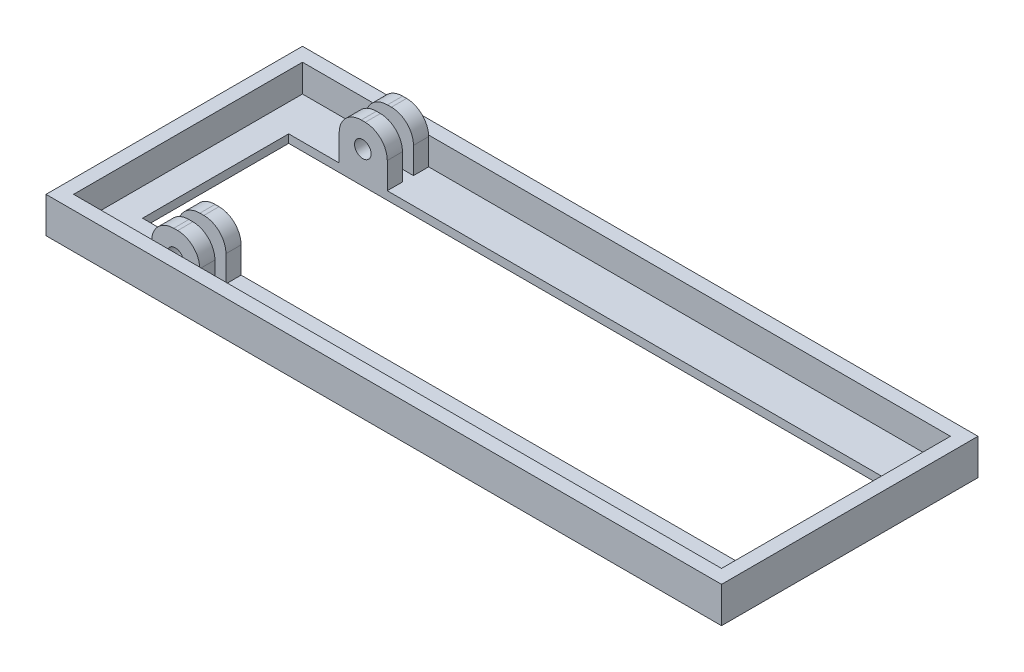
SolidWorks part; units mm, degrees
ref_plane "Front Plane" through (0, 0, 0) normal (0, 0, 1) x (1, 0, 0)
ref_plane "Top Plane" through (0, 0, 0) normal (0, 1, 0) x (1, 0, 0)
ref_plane "Right Plane" through (0, 0, 0) normal (1, 0, 0) x (0, 0, -1)
sketch "Sketch1" plane through (0, 0, 0) normal (0, 1, 0) x (1, 0, 0)
  line L0 (1125.8144, 1330.2208) -> (1275.8144, 1330.2208) construction
  line L1 (1275.8144, 1330.2208) -> (1275.8144, 1130.2208) construction
  line L2 (3575.3144, 400.2208) -> (3575.3144, 600.2208) construction
  line L3 (3575.3144, 600.2208) -> (3425.3144, 600.2208) construction
  line L5 (1275.8144, 1130.2208) -> (3425.3144, 1130.2208)
  line L6 (1275.8144, 1130.2208) -> (1275.8144, 600.2208)
  line L7 (1275.8144, 600.2208) -> (3425.3144, 600.2208)
  line L8 (3425.3144, 1130.2208) -> (3425.3144, 600.2208)
  line L13 (1125.8144, 1330.2208) -> (3575.3144, 1330.2208)
  line L14 (1125.8144, 1330.2208) -> (1125.8144, 400.2208)
  line L15 (1125.8144, 400.2208) -> (3575.3144, 400.2208)
  line L16 (3575.3144, 1330.2208) -> (3575.3144, 400.2208)
sketch "Sketch4" plane through (0, 0, 0) normal (0, 1, 0) x (1, 0, 0)
  line L0 (1125.8144, 1330.2208) -> (1275.8144, 1330.2208) construction
  line L1 (1275.8144, 1330.2208) -> (1275.8144, 1130.2208) construction
  line L2 (3575.3144, 400.2208) -> (3575.3144, 600.2208) construction
  line L3 (3575.3144, 600.2208) -> (3425.3144, 600.2208) construction
  line L4 (1275.8144, 1130.2208) -> (3425.3144, 1130.2208)
  line L5 (1275.8144, 1130.2208) -> (1275.8144, 600.2208)
  line L6 (1275.8144, 600.2208) -> (3425.3144, 600.2208)
  line L7 (3425.3144, 1130.2208) -> (3425.3144, 600.2208)
  line L8 (1125.8144, 1330.2208) -> (3575.3144, 1330.2208)
  line L9 (1125.8144, 1330.2208) -> (1125.8144, 400.2208)
  line L10 (1125.8144, 400.2208) -> (3575.3144, 400.2208)
  line L11 (3575.3144, 1330.2208) -> (3575.3144, 400.2208)
extrude "Boss-Extrude2" add sketch "Sketch4" along normal blind 30
sketch "Sketch5" plane through (0, 30, 0) normal (0, 1, 0) x (1, 0, 0)
  line L0 (1175.8144, 1280.2208) -> (1175.8144, 450.2208)
  line L1 (2350.5644, 1330.2208) -> (2350.5644, 400.2208) construction
  line L2 (3575.3144, 1330.2208) -> (1125.8144, 1330.2208) construction
  line L3 (1125.8144, 1330.2208) -> (1125.8144, 400.2208)
  line L4 (1125.8144, 400.2208) -> (3575.3144, 400.2208)
  line L5 (3575.3144, 1330.2208) -> (3575.3144, 400.2208)
  line L6 (3525.3144, 1280.2208) -> (3525.3144, 450.2208)
  line L9 (1125.8144, 400.2208) -> (3575.3144, 400.2208) construction
  line L10 (1175.8144, 1280.2208) -> (3525.3144, 1280.2208)
  line L11 (1175.8144, 450.2208) -> (3525.3144, 450.2208)
  line L12 (3575.3144, 1330.2208) -> (1125.8144, 1330.2208)
  point P7 (2350.5644, 450.2208)
  point P17 (2350.5644, 1280.2208)
sketch "Sketch6" plane through (0, 30, 0) normal (0, 1, 0) x (1, 0, 0)
  line L0 (1175.8144, 1280.2208) -> (1175.8144, 450.2208)
  line L1 (2350.5644, 1330.2208) -> (2350.5644, 400.2208) construction
  line L2 (1125.8144, 1330.2208) -> (1125.8144, 400.2208)
  line L3 (1125.8144, 400.2208) -> (3575.3144, 400.2208)
  line L4 (3575.3144, 1330.2208) -> (3575.3144, 400.2208)
  line L5 (3525.3144, 1280.2208) -> (3525.3144, 450.2208)
  line L6 (1175.8144, 1280.2208) -> (3525.3144, 1280.2208)
  line L7 (1175.8144, 450.2208) -> (3525.3144, 450.2208)
  line L8 (3575.3144, 1330.2208) -> (1125.8144, 1330.2208)
  point P6 (2350.5644, 450.2208)
  point P10 (2350.5644, 1280.2208)
extrude "Boss-Extrude3" add sketch "Sketch6" along normal blind 100
sketch "Sketch7" plane through (0, 30, 0) normal (0, 1, 0) x (1, 0, 0)
  line L0 (1275.8144, 1130.2208) -> (1546.0948, 1130.2208) construction
  line L1 (3425.3144, 1130.2208) -> (1275.8144, 1130.2208) construction
  line L2 (3525.3144, 1280.2208) -> (1175.8144, 1280.2208) construction
  line L3 (1275.8144, 865.2208) -> (3425.3144, 865.2208) construction
  line L4 (1458.8863, 1130.2208) -> (1458.8863, 1280.2208)
  line L5 (1458.8863, 1280.2208) -> (1633.3034, 1280.2208)
  line L6 (1633.3034, 1130.2208) -> (1633.3034, 1280.2208)
  line L7 (1275.8144, 1130.2208) -> (1275.8144, 600.2208) construction
  line L8 (3425.3144, 600.2208) -> (3425.3144, 1130.2208) construction
  line L9 (1458.8863, 1130.2208) -> (1633.3034, 1130.2208)
  line L10 (1458.8863, 600.2208) -> (1633.3034, 600.2208)
  line L11 (1633.3034, 600.2208) -> (1633.3034, 450.2208)
  line L12 (1458.8863, 450.2208) -> (1633.3034, 450.2208)
  line L13 (1458.8863, 600.2208) -> (1458.8863, 450.2208)
sketch "Sketch8" plane through (0, 30, 0) normal (0, 1, 0) x (1, 0, 0)
  line L0 (1275.8144, 1130.2208) -> (1546.0948, 1130.2208) construction
  line L1 (1458.8863, 1130.2208) -> (1458.8863, 1280.2208)
  line L2 (1458.8863, 1280.2208) -> (1633.3034, 1280.2208)
  line L3 (1633.3034, 1130.2208) -> (1633.3034, 1280.2208)
  line L4 (1458.8863, 1130.2208) -> (1633.3034, 1130.2208)
  line L5 (1458.8863, 600.2208) -> (1633.3034, 600.2208)
  line L6 (1633.3034, 600.2208) -> (1633.3034, 450.2208)
  line L7 (1458.8863, 450.2208) -> (1633.3034, 450.2208)
  line L8 (1458.8863, 600.2208) -> (1458.8863, 450.2208)
extrude "Boss-Extrude4" add sketch "Sketch8" along normal blind 175
sketch "Sketch9" plane through (0, 0, -1130.2208) normal (0, 0, 1) x (1, 0, 0)
  line L5 (1631.8345, 203.6281) -> (1457.4175, 29.211) construction
  circle A0 centre (1544.626, 116.4196) radius 30
sketch "Sketch10" plane through (0, 0, -1130.2208) normal (0, 0, 1) x (1, 0, 0)
  circle A0 centre (1544.626, 116.4196) radius 30
extrude "Cut-Extrude1" cut sketch "Sketch10" against normal blind 150 and the other way blind 680
fillet "Fillet1" radius 80 4 edges at (1633.3034, 205, -525.2208) (1458.8863, 205, -525.2208) (1458.8863, 205, -1205.2208) (1633.3034, 205, -1205.2208)
sketch "Sketch11" plane through (1633.3034, 0, 0) normal (1, 0, 0) x (0, 0, -1)
  line L0 (1205.2208, 30) -> (1225.2208, 30) construction
  line L1 (1130.2208, 30) -> (1280.2208, 30) construction
  line L2 (1205.2208, 30) -> (1185.2208, 30) construction
  line L3 (1185.2208, 30) -> (1185.2208, 230)
  line L4 (1225.2208, 30) -> (1225.2208, 230)
  line L5 (1185.2208, 230) -> (1225.2208, 230)
  line L6 (1185.2208, 30) -> (1225.2208, 30)
  line L7 (600.2208, 30) -> (1130.2208, 30) construction
  line L8 (1130.2208, 125) -> (1130.2208, 30) construction
  line L9 (865.2208, 30) -> (865.2208, 311.778) construction
  line L10 (525.2208, 30) -> (545.2208, 30) construction
  line L11 (525.2208, 30) -> (505.2208, 30) construction
  line L12 (545.2208, 30) -> (505.2208, 30)
  line L13 (545.2208, 230) -> (505.2208, 230)
  line L14 (505.2208, 30) -> (505.2208, 230)
  line L15 (545.2208, 30) -> (545.2208, 230)
sketch "Sketch12" plane through (1633.3034, 0, 0) normal (1, 0, 0) x (0, 0, -1)
  line L0 (1205.2208, 30) -> (1225.2208, 30) construction
  line L1 (1205.2208, 30) -> (1185.2208, 30) construction
  line L2 (1185.2208, 30) -> (1185.2208, 230)
  line L3 (1225.2208, 30) -> (1225.2208, 230)
  line L4 (1185.2208, 230) -> (1225.2208, 230)
  line L5 (1185.2208, 30) -> (1225.2208, 30)
  line L6 (600.2208, 30) -> (1130.2208, 30) construction
  line L7 (865.2208, 30) -> (865.2208, 311.778) construction
  line L8 (525.2208, 30) -> (545.2208, 30) construction
  line L9 (525.2208, 30) -> (505.2208, 30) construction
  line L10 (545.2208, 30) -> (505.2208, 30)
  line L11 (545.2208, 230) -> (505.2208, 230)
  line L12 (505.2208, 30) -> (505.2208, 230)
  line L13 (545.2208, 30) -> (545.2208, 230)
extrude "Cut-Extrude2" cut sketch "Sketch12" against normal blind 184
